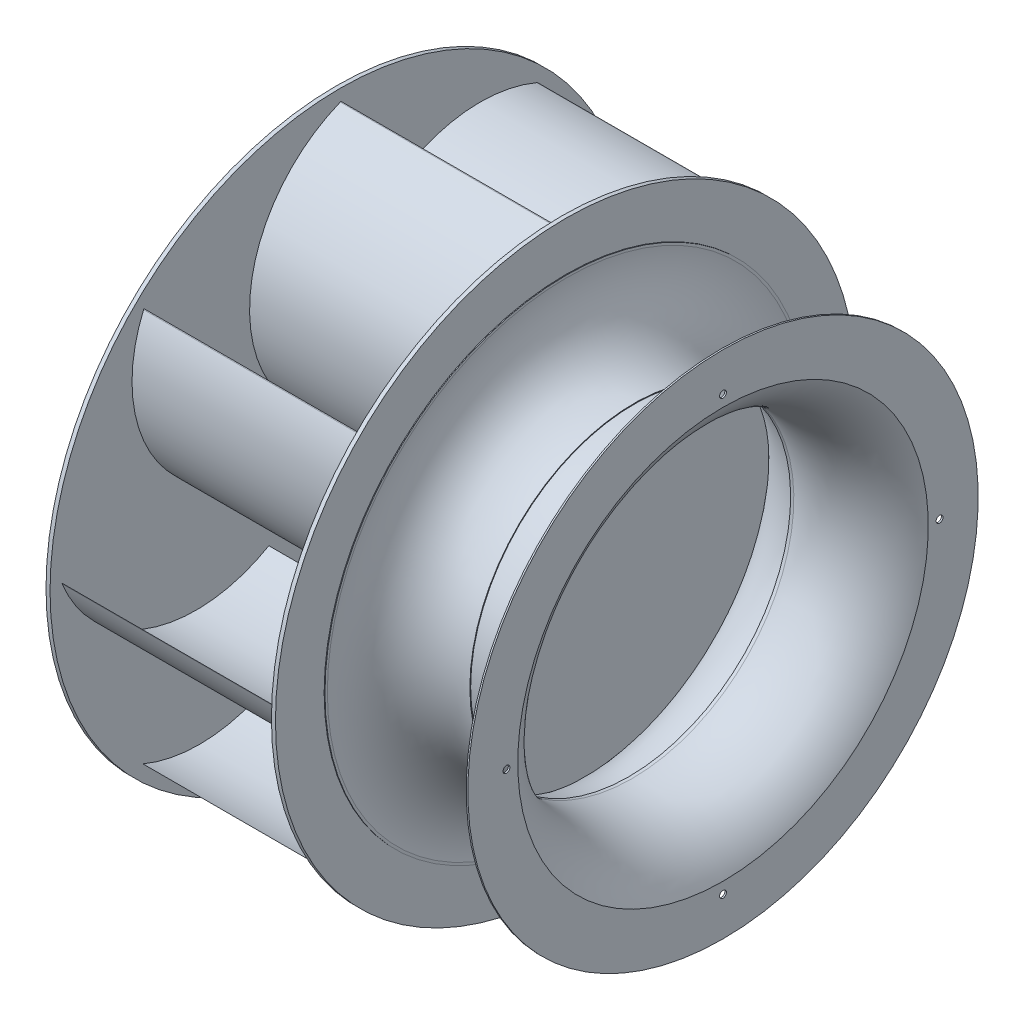
SolidWorks part; units mm, degrees
ref_plane "Front Plane" through (0, 0, 0) normal (0, 0, 1) x (1, 0, 0)
ref_plane "Top Plane" through (0, 0, 0) normal (0, 1, 0) x (1, 0, 0)
ref_plane "Right Plane" through (0, 0, 0) normal (1, 0, 0) x (0, 0, -1)
sketch "Sketch1" plane through (0, 0, 0) normal (0, 0, 1) x (1, 0, 0)
  line L0 (0, 0) -> (831.9083, 0) construction
  line L1 (0, 0) -> (0, 109)
  line L2 (5, 114) -> (69.5, 114)
  line L3 (69.5, 114) -> (69.5, 138)
  line L4 (69.5, 138) -> (89.5, 138)
  line L5 (89.5, 138) -> (89.5, 98)
  line L6 (89.5, 98) -> (91.5, 98)
  line L7 (91.5, 98) -> (91.5, 133)
  line L8 (91.5, 133) -> (94.5, 133)
  line L9 (94.5, 133) -> (94.5, 98)
  line L10 (94.5, 98) -> (96.5, 98)
  line L11 (96.5, 98) -> (96.5, 0)
  line L12 (96.5, 0) -> (0, 0)
  arc A0 (5, 114) -> (0, 109) centre (5, 109) ccw
  point P16 (0, 114)
  dimension "D10" = 5
  dimension "D1" = 114
  dimension "D2" = 24
  dimension "D3" = 69.5
  dimension "D4" = 40
  dimension "D5" = 35
  dimension "D6" = 2
  dimension "D7" = 20
  dimension "D8" = 3
  dimension "D9" = 27
revolve "Revolve1" add sketch "Sketch1" angle 360 about L0
sketch "Sketch2" plane through (96.5, 0, 0) normal (1, 0, 0) x (0, 0, -1)
  circle A0 centre (0, 0) radius 360.5
  dimension "D1" = 721
extrude "Extrude1" add sketch "Sketch2" along normal blind 5
sketch "Sketch9" plane through (96.5, 0, 0) normal (-1, 0, 0) x (0, 0, 1)
  circle A0 centre (0, 0) radius 355.5
  circle A1 centre (0, 0) radius 100
  circle A2 centre (0, 0) radius 360.5 construction
  dimension "D1" = 5
  dimension "D2" = 200
extrude "Extrude7" cut sketch "Sketch9" against normal blind 3
ref_plane "Plane1" through (376.5, 0, 0) normal (1, 0, 0) x (0, 0, -1)
sketch "Sketch3" plane through (376.5, 0, 0) normal (1, 0, 0) x (0, 0, -1)
  circle A0 centre (0, 0) radius 360.5
  dimension "D1" = 721
extrude "Extrude2" add sketch "Sketch3" along normal blind 5 separate body
sketch "Sketch4" plane through (101.5, 0, 0) normal (1, 0, 0) x (0, 0, -1)
  line L0 (0, 0) -> (0, 345.5) construction
  line L1 (0, 0) -> (254.912, 254.912) construction
  line L2 (0, 125) -> (0.866, 124.5)
  line L3 (244.3054, 244.3054) -> (245.1714, 243.8054)
  circle A0 centre (0, 0) radius 345.5 construction
  circle A1 centre (0, 0) radius 360.5 construction
  circle A2 centre (0, 0) radius 125 construction
  arc A3 (0, 125) -> (244.3054, 244.3054) centre (173.926, 78.6348) cw
  arc A4 (0.866, 124.5) -> (245.1714, 243.8054) centre (174.7921, 78.1348) cw
  dimension "D1" = 15
  dimension "D2" = 250
  dimension "D6" = 180
  dimension "D7" = 180
  dimension "D3" = 45
  dimension "D4" = 60
  dimension "D5" = 1
extrude "Extrude3" add sketch "Sketch4" along normal up to surface (280 mm away) up to face at (381.5, 0, -360.5)
ref_axis "Axis1" through (253.5503, 0, 0) along (-1, 0, 0)
pattern_circular "CirPattern1" count 8 over 360 about axis through (253.5503, 0, 0) along (-1, 0, 0) of "Extrude3"
sketch "Sketch5" plane through (0, 0, 0) normal (0, 0, 1) x (1, 0, 0)
  line L0 (0, 0) -> (527.2916, 0) construction
  line L1 (253.5503, 0) -> (75.411, 0) construction
  line L2 (381.5, 300) -> (382.5, 300)
  line L3 (382.5, 300) -> (382.5, 297)
  line L4 (381.5, 300) -> (381.5, 297)
  line L5 (466.5, 204) -> (466.5, 203)
  line L6 (69.5, 138) -> (69.5, -138) construction
  line L7 (381.5, -360.5) -> (381.5, 360.5) construction
  arc A0 (382.5, 297) -> (466.5, 204) centre (467.1225, 288.9977) ccw
  arc A1 (381.5, 297) -> (466.5, 203) centre (466.022, 287.9987) ccw
  dimension "D7" = 85
  dimension "D8" = 85
  dimension "D1" = 203
  dimension "D2" = 1
  dimension "D3" = 1
  dimension "D4" = 3
  dimension "D5" = 300
  dimension "D6" = 397
revolve "Revolve2" add sketch "Sketch5" angle 360 about L0
ref_plane "Plane3" through (577, 0, 0) normal (1, 0, 0) x (0, 0, -1)
sketch "Sketch6" plane through (0, 0, 0) normal (0, 0, 1) x (1, 0, 0)
  line L0 (577, 317) -> (575, 317)
  line L1 (577, -251.35) -> (577, 251.35) construction
  line L2 (575, 317) -> (575, 255)
  line L3 (0, 0) -> (615.1417, 0) construction
  line L4 (0, 114) -> (0, -114) construction
  line L5 (253.5503, 0) -> (75.411, 0) construction
  line L6 (577, 317) -> (577, 255)
  line L7 (460, 203) -> (464, 203)
  line L8 (460, 203) -> (460, 201)
  line L9 (460, 201) -> (464, 201)
  arc A0 (464, 203) -> (575, 255) centre (485.9789, 300.5548) ccw
  arc A1 (464, 201) -> (577, 255) centre (486.883, 298.3466) ccw
  dimension "D7" = 100
  dimension "D8" = 100
  dimension "D1" = 317
  dimension "D2" = 2
  dimension "D3" = 255
  dimension "D4" = 117
  dimension "D5" = 203
  dimension "D6" = 4
revolve "Revolve3" add sketch "Sketch6" angle 360 about L3
sketch "Sketch7" plane through (577, 0, 0) normal (1, 0, 0) x (0, 0, -1)
  line L0 (0, 0) -> (0, 269) construction
  circle A0 centre (0, 0) radius 269 construction
  circle A1 centre (0, 269) radius 4.25
  dimension "D1" = 538
  dimension "D2" = 8.5
extrude "Extrude5" cut sketch "Sketch7" against normal blind 5
pattern_circular "CirPattern2" count 4 over 360 about axis through (253.5503, 0, 0) along (-1, 0, 0) of "Extrude5"
sketch "Sketch8" plane through (0, 0, 0) normal (1, 0, 0) x (0, 0, -1)
  line L0 (0, 0) -> (0, 126) construction
  circle A0 centre (0, 0) radius 126 construction
  circle A1 centre (0, 126) radius 5
  dimension "D1" = 252
  dimension "D2" = 10
extrude "Extrude6" cut sketch "Sketch8" along normal up to surface (89.5 mm away) up to face at (89.5, 0, 138)
pattern_circular "CirPattern3" count 8 over 360 about axis through (253.5503, 0, 0) along (-1, 0, 0) of "Extrude6"
